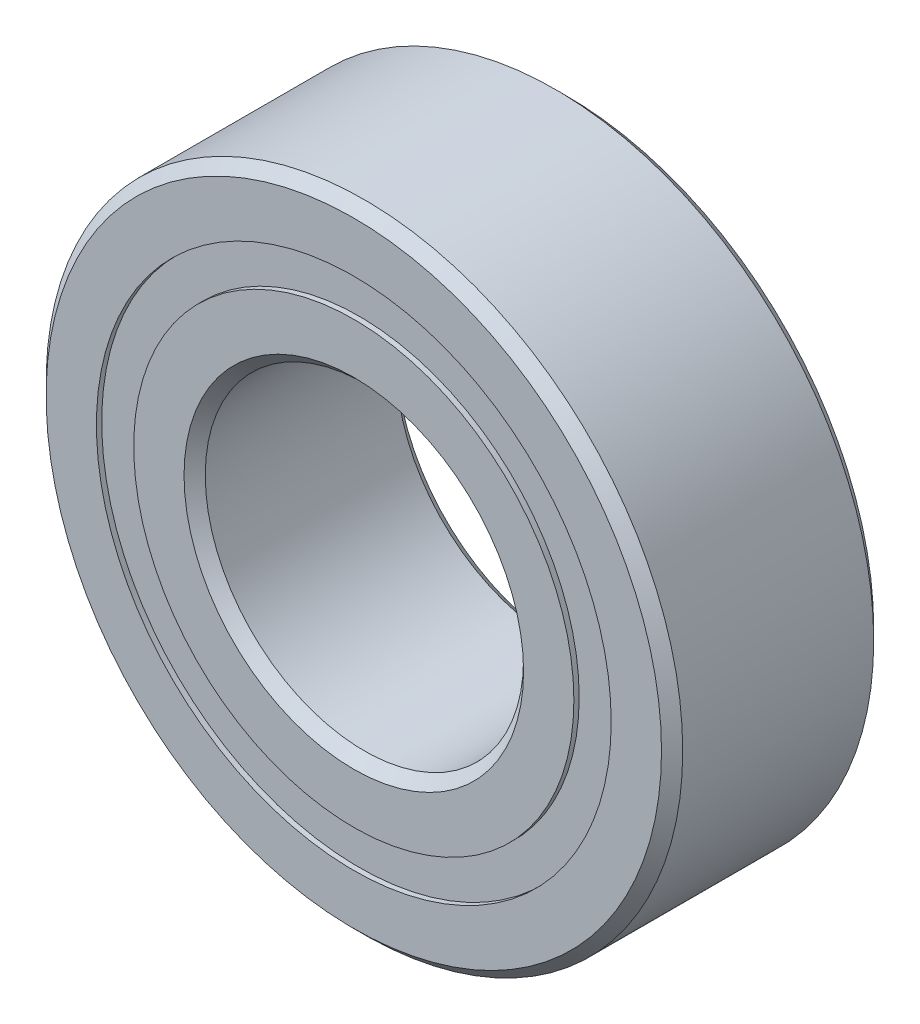
SolidWorks part; units mm, degrees
material "AISI 304"
ref_plane "Front Plane" through (0, 0, 0) normal (0, 0, 1) x (1, 0, 0)
ref_plane "Top Plane" through (0, 0, 0) normal (0, 1, 0) x (1, 0, 0)
ref_plane "Right Plane" through (0, 0, 0) normal (1, 0, 0) x (0, 0, -1)
sketch "Sketch1" plane through (0, 0, 0) normal (1, 0, 0) x (0, 0, -1)
  line L0 (-1.5875, 0) -> (1.5875, 0) construction
  line L1 (0, 4.7625) -> (0, -4.7625) construction
  line L2 (1.4288, 4.7625) -> (-1.4288, 4.7625)
  line L3 (-1.4288, 4.7625) -> (-1.5875, 4.6037)
  line L4 (-1.5875, 4.6037) -> (-1.5875, 3.851)
  line L5 (-1.5875, 3.851) -> (-0.7056, 3.851)
  line L6 (1.5875, 3.851) -> (0.7056, 3.851)
  line L7 (1.5875, 4.6037) -> (1.5875, 3.851)
  line L8 (1.4288, 4.7625) -> (1.5875, 4.6037)
  line L9 (0, 4.7625) -> (0, 3.5719) construction
  line L10 (0, 3.5719) -> (0, 2.3813) construction
  arc A0 (-0.7056, 3.851) -> (0.7056, 3.851) centre (0, 3.5719) cw
  point P14 (0, 2.3813)
  dimension "Width" = 3.175
  dimension "OD" = 9.525
  dimension "D1" = 45
  dimension "D2" = 0.1588
  dimension "D3" = 1.4111
  dimension "D4" = 0.2791
revolve "Revolve1" add sketch "Sketch1" angle 360 about L0
sketch "Sketch3" plane through (0, 0, 0) normal (1, 0, 0) x (0, 0, -1)
  line L0 (-0.7056, 3.2928) -> (-1.5875, 3.2928)
  line L1 (-1.5875, 4.6037) -> (-1.5875, 3.851) construction
  line L2 (-1.4288, 4.7625) -> (-1.5875, 4.6037) construction
  line L3 (-1.5875, 3.2928) -> (-1.5875, 2.54)
  line L5 (-1.5875, 2.54) -> (-1.4288, 2.3813)
  line L6 (-1.4288, 2.3813) -> (1.4288, 2.3813)
  line L7 (1.4288, 4.7625) -> (1.4288, -4.7625) construction
  line L8 (1.4288, 2.3813) -> (1.5875, 2.54)
  line L9 (1.5875, -4.6037) -> (1.5875, 4.6037) construction
  line L10 (1.5875, 2.54) -> (1.5875, 3.2928)
  line L11 (1.5875, 3.2928) -> (0.7056, 3.2928)
  line L12 (0, 4.7625) -> (0, -4.7625) construction
  line L13 (1.4288, 4.7625) -> (1.5875, 4.6037) construction
  arc A1 (0.7056, 3.2928) -> (-0.7056, 3.2928) centre (0, 3.5719) cw
  arc A2 (0.7056, 3.851) -> (-0.7056, 3.851) centre (0, 3.5719) ccw construction
revolve "Revolve3" add sketch "Sketch3" angle 360 about L0
sketch "Sketch4" plane through (0, 0, 0) normal (1, 0, 0) x (0, 0, -1)
  line L0 (-0.7588, 3.5719) -> (0.7588, 3.5719)
  arc A2 (-0.7588, 3.5719) -> (0.7588, 3.5719) centre (0, 3.5719) cw
  arc A3 (0.7056, 3.851) -> (-0.7056, 3.851) centre (0, 3.5719) ccw construction
revolve "Revolve4" add sketch "Sketch4" angle 360 about L0
ref_axis "Axis1" through (0, 0, -1.5875) along (0, 0, 1)
pattern_circular "CirPattern1" count 12 every 30 about axis through (0, 0, -1.5875) along (0, 0, 1) of bodies 104
sketch "Sketch5" plane through (0, 0, 0) normal (1, 0, 0) x (0, 0, -1)
  line L0 (-1.5875, 3.851) -> (-0.7056, 3.851) construction
  line L1 (-1.5081, 3.851) -> (-0.7588, 3.851)
  line L2 (-1.5081, 3.851) -> (-1.5081, 3.2928)
  line L3 (-1.5081, 3.2928) -> (-0.7588, 3.2928)
  line L4 (-0.7588, 3.851) -> (-0.7588, 3.2928)
  line L5 (-0.7056, 3.2928) -> (-1.5875, 3.2928) construction
  line L6 (1.5875, 3.851) -> (0.7056, 3.851) construction
  line L7 (1.5081, 3.851) -> (0.7588, 3.851)
  line L8 (1.5081, 3.851) -> (1.5081, 3.2928)
  line L9 (1.5081, 3.2928) -> (0.7588, 3.2928)
  line L10 (0.7588, 3.851) -> (0.7588, 3.2928)
  line L11 (1.5875, 3.2928) -> (0.7056, 3.2928) construction
  line L12 (-1.4288, 4.7625) -> (-1.5875, 4.6037) construction
  point P18 (-1.5081, 4.6831)
revolve "Revolve5" add sketch "Sketch5" angle 360 about L0
equation "\"D2@Sketch1\" = \"Width@Sketch1\"*.05"
equation "\"D3@Sketch1\" = \"Width@Sketch1\"/2.25"
equation "\"D4@Sketch1\" = (((\"OD@Sketch1\"-\"Width@Sketch1\")/2)/3.25)/3.5"
equation "\"D2@CirPattern1\" = 360/\"Balls@CirPattern1\""
